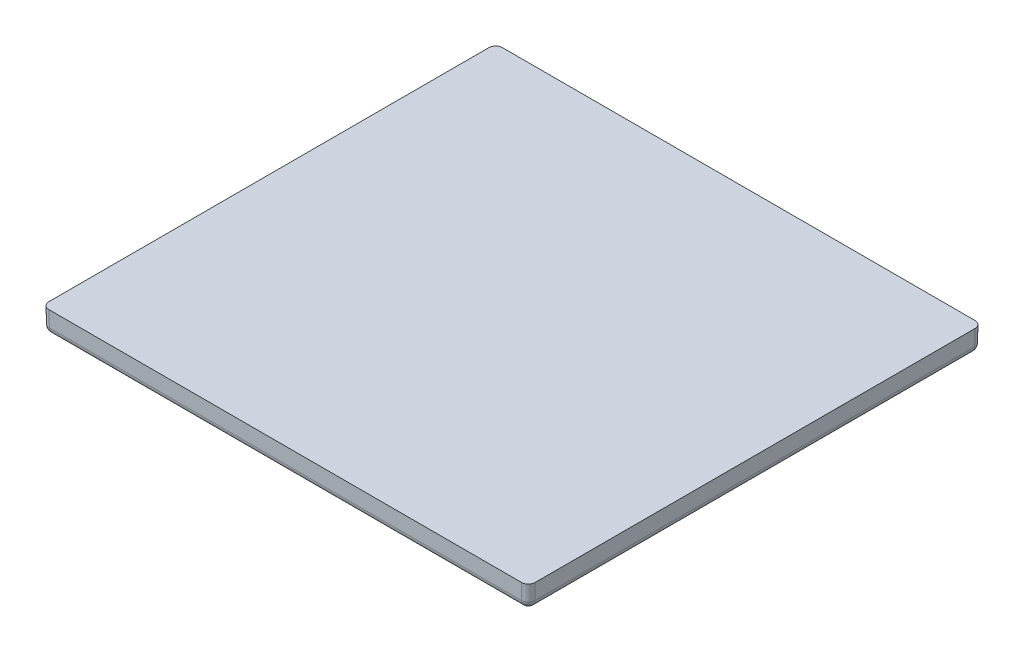
SolidWorks part; units mm, degrees
ref_plane "Front Plane" through (0, 0, 0) normal (0, 0, 1) x (1, 0, 0)
ref_plane "Top Plane" through (0, 0, 0) normal (0, 1, 0) x (1, 0, 0)
ref_plane "Right Plane" through (0, 0, 0) normal (1, 0, 0) x (0, 0, -1)
ref_axis "Axis1" through (-33.0333, 0, 0) along (1, 0, 0)
ref_axis "Axis2" through (0, 24.5224, 0) along (0, -1, 0)
ref_axis "Axis3" through (0, 0, -30.7663) along (0, 0, 1)
sketch "Sketch1" plane through (0, 0, 0) normal (0, 1, 0) x (1, 0, 0)
  line L1 (-107.75, -100.5) -> (107.75, -100.5)
  line L2 (-107.75, -100.5) -> (-107.75, 100.5)
  line L3 (-107.75, 100.5) -> (107.75, 100.5)
  line L4 (107.75, -100.5) -> (107.75, 100.5)
  line L5 (-107.75, -100.5) -> (107.75, 100.5) construction
  line L6 (-107.75, 100.5) -> (107.75, -100.5) construction
  point P0 (0, 0)
  dimension "D1" = 215.5
  dimension "D2" = 201
extrude "Boss-Extrude1" add sketch "Sketch1" along normal blind 10 draft 1 draft outward yes
fillet "Fillet1" radius 3 8 edges at (0, 0, -100.5) (-107.8373, 5, -100.5873) (107.8373, 5, -100.5873) (107.75, 0, 0) (107.8373, 5, 100.5873) (-107.75, 0, 0) (0, 0, 100.5) (-107.8373, 5, 100.5873)
